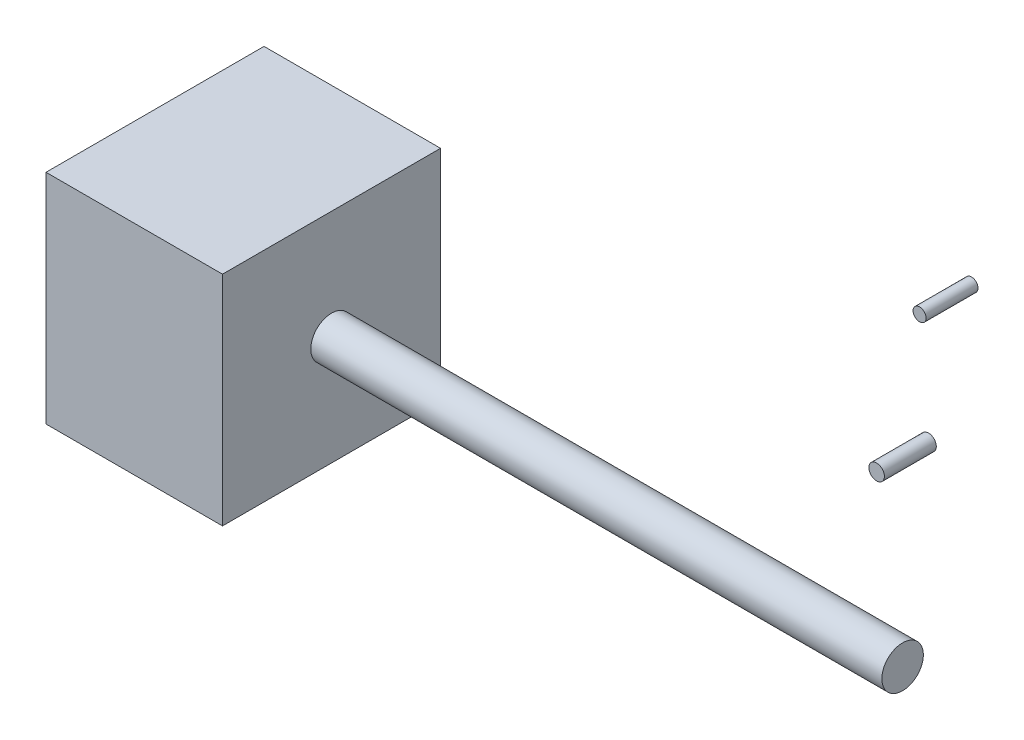
SolidWorks part; units mm, degrees
ref_plane "前视基准面" through (0, 0, 0) normal (0, 0, 1) x (1, 0, 0)
ref_plane "上视基准面" through (0, 0, 0) normal (0, 1, 0) x (1, 0, 0)
ref_plane "右视基准面" through (0, 0, 0) normal (1, 0, 0) x (0, 0, -1)
sketch "草图1" plane through (0, 0, 0) normal (1, 0, 0) x (0, 0, -1)
  line L1 (-21, -21) -> (21, -21)
  line L2 (-21, -21) -> (-21, 21)
  line L3 (-21, 21) -> (21, 21)
  line L4 (21, -21) -> (21, 21)
  line L5 (-21, -21) -> (21, 21) construction
  line L6 (-21, 21) -> (21, -21) construction
  point P0 (0, 0)
  dimension "D1" = 42
  dimension "D2" = 42
extrude "凸台-拉伸1" add sketch "草图1" against normal blind 44
sketch "草图2" plane through (0, 0, 0) normal (1, 0, 0) x (0, 0, -1)
  circle A0 centre (0, 0) radius 4
extrude "凸台-拉伸2" add sketch "草图2" along normal blind 100
sketch "草图5" plane through (0, 0, 0) normal (0, 0, 1) x (1, 0, 0)
  circle A0 centre (100, 35) radius 1.5 construction
  circle A1 centre (100, 35) radius 1.5
  dimension "D1" = 3
extrude "凸台-拉伸3" add sketch "草图5" along normal mid plane 10 separate body
sketch "草图6" plane through (0, 0, 0) normal (0, 0, 1) x (1, 0, 0)
  line L0 (108.2772, 65.4293) -> (100, 35) construction
  line L1 (100, 35) -> (184.4213, 35) construction
  circle A0 centre (108.2772, 65.4293) radius 1.25
  dimension "D1" = 31.535
  dimension "D3" = 2.5
  dimension "D2" = 74.783
extrude "凸台-拉伸4" add sketch "草图6" along normal mid plane 10 separate body
extrude "切除-拉伸1" cut sketch "草图1<2>" against normal blind 10
sketch "草图1<2>" plane through (0, 0, 0) normal (1, 0, 0) x (0, 0, -1) same geometry as "草图1"
extrude "凸台-拉伸5" add sketch "草图2<2>" against normal blind 20
sketch "草图2<2>" plane through (0, 0, 0) normal (1, 0, 0) x (0, 0, -1) same geometry as "草图2"
sketch "草图8" plane through (-10, 0, 0) normal (1, 0, 0) x (0, 0, -1)
  line L0 (-35.5389, 0) -> (34.4488, 0) construction
  line L1 (-21, 30) -> (21, 30)
  line L2 (-21, 30) -> (-21, -30)
  line L3 (-21, -30) -> (21, -30)
  line L4 (21, -21) -> (21, 21)
  line L5 (21, 21) -> (-21, 21)
  line L6 (-21, 21) -> (-21, -21)
  line L7 (-21, -21) -> (21, -21)
  line L8 (21, -21) -> (21, 21)
  line L10 (-21, 21) -> (-21, -21)
  line L12 (21, 30) -> (21, -30)
  circle A0 centre (0, 0) radius 4.5
  dimension "D2" = 30
  dimension "D3" = 30
  dimension "D1" = 0
